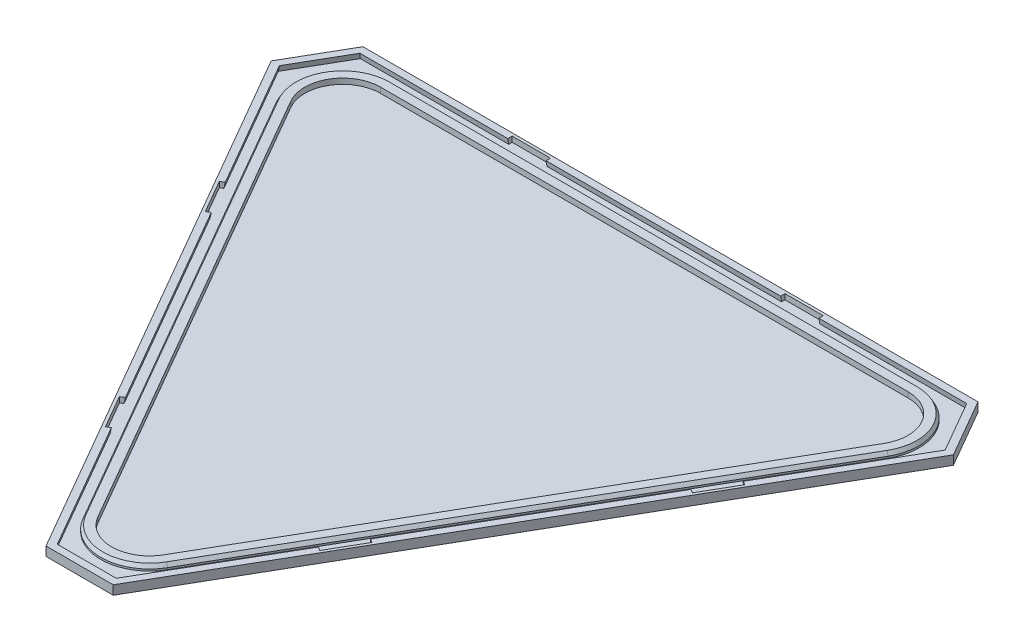
SolidWorks part; units mm, degrees
ref_plane "Plan de face" through (0, 0, 0) normal (0, 0, 1) x (1, 0, 0)
ref_plane "Plan de dessus" through (0, 0, 0) normal (0, 1, 0) x (1, 0, 0)
ref_plane "Plan de droite" through (0, 0, 0) normal (1, 0, 0) x (0, 0, -1)
sketch "Esquisse2" plane through (0, 0, 0) normal (0, 1, 0) x (1, 0, 0)
  line L3 (-93.7624, 43.4671) -> (-52.85, -27.3953) construction
  line L4 (9.2376, -102.9342) -> (50.15, -32.0718) construction
  line L5 (84.5248, 59.4671) -> (2.7, 59.4671) construction
  line L6 (-93.7624, 43.4671) -> (-84.5248, 59.4671)
  line L7 (84.5248, 59.4671) -> (93.7624, 43.4671)
  line L8 (9.2376, -102.9342) -> (-9.2376, -102.9342)
  line L9 (-93.7624, 43.4671) -> (-9.2376, -102.9342)
  line L10 (9.2376, -102.9342) -> (93.7624, 43.4671)
  line L11 (84.5248, 59.4671) -> (-84.5248, 59.4671)
  line L12 (93.7624, 43.4671) -> (84.5248, 59.4671) construction
  line L13 (-9.2376, -102.9342) -> (9.2376, -102.9342) construction
  line L14 (-84.5248, 59.4671) -> (-93.7624, 43.4671) construction
  point P16 (0, 0)
extrude "smartleaf_triangle_multi" add sketch "Esquisse2" along normal blind 1
sketch "Esquisse5" plane through (0, 1, 0) normal (0, 1, 0) x (1, 0, 0)
  line L19 (-93.7624, 43.4671) -> (-9.2376, -102.9342)
  line L20 (-9.2376, -102.9342) -> (9.2376, -102.9342)
  line L21 (9.2376, -102.9342) -> (93.7624, 43.4671)
  line L26 (93.7624, 43.4671) -> (84.5248, 59.4671)
  line L27 (84.5248, 59.4671) -> (-84.5248, 59.4671)
  line L32 (-84.5248, 59.4671) -> (-93.7624, 43.4671)
  line L37 (-93.7624, 43.4671) -> (-9.2376, -102.9342)
  line L38 (-9.2376, -102.9342) -> (9.2376, -102.9342)
  line L39 (9.2376, -102.9342) -> (93.7624, 43.4671)
  line L44 (93.7624, 43.4671) -> (84.5248, 59.4671)
  line L45 (84.5248, 59.4671) -> (-84.5248, 59.4671)
  line L50 (-84.5248, 59.4671) -> (-93.7624, 43.4671)
  dimension "D1" = 0
extrude "Extru.-Mince1" add sketch "Esquisse5" along normal blind 1.5 draft 10 thin draft outward yes thin type one direction reverse wall 1.7
sketch "Esquisse6" plane through (0, 0, 0) normal (0, -1, 0) x (1, 0, 0)
  line L6 (-84.5248, -59.4671) -> (84.5248, -59.4671)
  line L7 (84.5248, -59.4671) -> (93.7624, -43.4671)
  line L8 (93.7624, -43.4671) -> (9.2376, 102.9342)
  line L9 (9.2376, 102.9342) -> (-9.2376, 102.9342)
  line L10 (-9.2376, 102.9342) -> (-93.7624, -43.4671)
  line L11 (-93.7624, -43.4671) -> (-84.5248, -59.4671)
  line L12 (-84.5248, -59.4671) -> (84.5248, -59.4671)
  line L13 (84.5248, -59.4671) -> (93.7624, -43.4671)
  line L14 (93.7624, -43.4671) -> (9.2376, 102.9342)
  line L15 (9.2376, 102.9342) -> (-9.2376, 102.9342)
  line L16 (-9.2376, 102.9342) -> (-93.7624, -43.4671)
  line L17 (-93.7624, -43.4671) -> (-84.5248, -59.4671)
  dimension "D1" = 0
extrude "Enlèv. de mat.-Extru.-Mince1" cut sketch "Esquisse6" against normal through all thin thin type one direction wall 1.5
sketch "Esquisse7" plane through (0, 1, 0) normal (0, 1, 0) x (1, 0, 0)
  line L0 (2.25, 59.4671) -> (-2.25, 59.4671)
  line L1 (2.25, 59.4671) -> (2.25, 55.3671)
  line L2 (-2.25, 59.4671) -> (-2.25, 55.3671)
  line L3 (2.25, 55.3671) -> (-2.25, 55.3671)
  line L4 (-84.5248, 59.4671) -> (84.5248, 59.4671) construction
  line L5 (46.8243, -29.6321) -> (49.0743, -25.735)
  line L6 (50.375, -31.6821) -> (46.8243, -29.6321)
  line L7 (50.375, -31.6821) -> (52.625, -27.785)
  line L8 (52.625, -27.785) -> (49.0743, -25.735)
  line L9 (-49.0743, -25.735) -> (-46.8243, -29.6321)
  line L10 (-52.625, -27.785) -> (-49.0743, -25.735)
  line L11 (-52.625, -27.785) -> (-50.375, -31.6821)
  line L12 (-50.375, -31.6821) -> (-46.8243, -29.6321)
  point P6 (0, 59.4671)
  point P7 (0, 59.4671)
  point P19 (0, 0)
  dimension "D1" = 4.1
  dimension "D2" = 4.5
  dimension "D3" = 3
extrude "Boss.-Extru.5" [suppressed] add sketch "Esquisse7" along normal up to surface (1.5 mm away)
sketch "Esquisse8" [suppressed] plane through (0, 1, 0) normal (0, 1, 0) x (1, 0, 0)
  line L0 (-2.25, 40.6446) -> (2.25, 40.6446) construction
  line L1 (-5, 40.6446) -> (5, 40.6446)
  line L2 (-5, 40.6446) -> (-5, 38.6446)
  line L3 (-5, 38.6446) -> (5, 38.6446)
  line L4 (5, 40.6446) -> (5, 38.6446)
  line L5 (37.6993, -15.9922) -> (32.6993, -24.6524)
  line L6 (37.6993, -15.9922) -> (35.9672, -14.9922)
  line L7 (35.9672, -14.9922) -> (30.9672, -23.6524)
  line L8 (32.6993, -24.6524) -> (30.9672, -23.6524)
  line L9 (-32.6993, -24.6524) -> (-37.6993, -15.9922)
  line L10 (-32.6993, -24.6524) -> (-30.9672, -23.6524)
  line L11 (-30.9672, -23.6524) -> (-35.9672, -14.9922)
  line L12 (-37.6993, -15.9922) -> (-35.9672, -14.9922)
  point P7 (0, 40.6446)
  point P8 (0, 40.6446)
  point P18 (0, 0)
  dimension "D1" = 10
  dimension "D2" = 2
  dimension "D3" = 3
extrude "Boss.-Extru.6" [suppressed] add sketch "Esquisse8" along normal blind 2.2
sketch "Esquisse9" [suppressed] plane through (0, 3.2, 0) normal (0, 1, 0) x (1, 0, 0)
  line L1 (0.6, 40.9446) -> (-0.6, 40.9446)
  line L2 (0.6, 40.9446) -> (0.6, 38.6446)
  line L3 (0.6, 38.6446) -> (-0.6, 38.6446)
  line L4 (-0.6, 40.9446) -> (-0.6, 38.6446)
  line L6 (35.1591, -20.9919) -> (35.7591, -19.9527)
  line L7 (35.1591, -20.9919) -> (33.1672, -19.8419)
  line L8 (33.1672, -19.8419) -> (33.7672, -18.8027)
  line L9 (35.7591, -19.9527) -> (33.7672, -18.8027)
  line L10 (-35.7591, -19.9527) -> (-35.1591, -20.9919)
  line L11 (-35.7591, -19.9527) -> (-33.7672, -18.8027)
  line L12 (-33.7672, -18.8027) -> (-33.1672, -19.8419)
  line L13 (-35.1591, -20.9919) -> (-33.1672, -19.8419)
  line L14 (-2.25, 40.6446) -> (2.25, 40.6446) construction
  line L15 (5, 40.6446) -> (-5, 40.6446) construction
  line L16 (-5, 38.6446) -> (5, 38.6446) construction
  point P4 (0, 40.9446)
  point P9 (0, 40.6446)
  point P21 (0, 0)
  dimension "D1" = 1.2
  dimension "D2" = 3
  dimension "D3" = 0.3
extrude "Boss.-Extru.7" [suppressed] add sketch "Esquisse9" along normal blind 3 and the other way up to next
sketch "Esquisse10" plane through (0, 2.5, 0) normal (0, 1, 0) x (1, 0, 0)
  line L0 (0, 59.4671) -> (0, 32.7785) construction
  line L1 (-32.25, 58.7026) -> (-42.75, 58.7026)
  line L2 (-32.25, 58.7026) -> (-32.25, 39.7025)
  line L3 (-32.25, 39.7025) -> (-42.75, 39.7025)
  line L4 (-42.75, 58.7026) -> (-42.75, 39.7025)
  line L5 (83.3906, 57.5026) -> (-83.3906, 57.5026) construction
  line L7 (-84.5248, 59.4671) -> (84.5248, 59.4671) construction
  line L8 (42.75, 58.7026) -> (42.75, 39.7025)
  line L9 (32.25, 39.7025) -> (42.75, 39.7025)
  line L10 (32.25, 58.7026) -> (32.25, 39.7025)
  line L11 (32.25, 58.7026) -> (42.75, 58.7026)
  line L12 (66.9629, -1.422) -> (72.2129, 7.6713)
  line L13 (66.9629, -1.422) -> (50.5084, 8.0781)
  line L14 (50.5084, 8.0781) -> (55.7584, 17.1713)
  line L15 (72.2129, 7.6713) -> (55.7584, 17.1713)
  line L16 (29.4629, -66.3739) -> (13.0084, -56.8738)
  line L17 (18.2584, -47.7806) -> (13.0084, -56.8738)
  line L18 (34.7129, -57.2806) -> (18.2584, -47.7806)
  line L19 (34.7129, -57.2806) -> (29.4629, -66.3739)
  line L20 (-34.7129, -57.2806) -> (-29.4629, -66.3739)
  line L21 (-34.7129, -57.2806) -> (-18.2584, -47.7806)
  line L22 (-18.2584, -47.7806) -> (-13.0084, -56.8738)
  line L23 (-29.4629, -66.3739) -> (-13.0084, -56.8738)
  line L24 (-72.2129, 7.6713) -> (-55.7584, 17.1713)
  line L25 (-50.5084, 8.0781) -> (-55.7584, 17.1713)
  line L26 (-66.9629, -1.422) -> (-50.5084, 8.0781)
  line L27 (-66.9629, -1.422) -> (-72.2129, 7.6713)
  point P11 (-37.5, 58.7026)
  point P35 (0, 0)
  dimension "D1" = 1.2
  dimension "D2" = 10.5
  dimension "D3" = 75
  dimension "D4" = 3
extrude "Enlèv. mat.-Extru.1" cut sketch "Esquisse10" against normal up to surface (1.5 mm away) up to face at (0, 1, 0)
sketch "Esquisse11" plane through (0, 1, 0) normal (0, 1, 0) x (1, 0, 0)
  line L6 (-12.1244, -90.9342) -> (-47.1189, -30.3218) construction
  line L7 (84.8135, 34.9671) -> (49.8189, -25.6453) construction
  line L8 (2.7, 55.9671) -> (72.6891, 55.9671) construction
  line L12 (11.6127, -90.4204) -> (84.1127, 35.1533)
  line L13 (-84.1127, 35.1533) -> (-11.6127, -90.4204)
  line L14 (72.5, 55.2671) -> (-72.5, 55.2671)
  arc A9 (84.1127, 35.1533) -> (72.5, 55.2671) centre (72.5, 41.8579) ccw
  arc A10 (-11.6127, -90.4204) -> (11.6127, -90.4204) centre (0, -83.7158) ccw
  arc A11 (-72.5, 55.2671) -> (-84.1127, 35.1533) centre (-72.5, 41.8579) ccw
  point P0 (0, -82.957)
  dimension "D4" = 145
  dimension "D1" = 0.7
  dimension "D2" = 0.7
  dimension "D3" = 0.7
extrude "Extru.-Mince2" add sketch "Esquisse11" along normal up to surface (1.5 mm away) separate body thin up to face at (0, 2.5, 0) thin type one direction reverse wall 3
sketch "Esquisse12" plane through (0, 1, 0) normal (0, 1, 0) x (1, 0, 0)
  line L0 (72.5, 52.2671) -> (-72.5, 52.2671) construction
  line L1 (-7.5, 40.7446) -> (7.5, 40.7446)
  line L2 (-7.5, 40.7446) -> (-7.5, 52.2671)
  line L3 (-7.5, 52.2671) -> (7.5, 52.2671)
  line L4 (7.5, 40.7446) -> (7.5, 52.2671)
  line L5 (-7.5, 35.7446) -> (-7.5, 40.7446) construction
  line L6 (7.5, 40.7446) -> (7.5, 35.7446) construction
  line L7 (1.75, 40.7446) -> (9.5, 40.7446) construction
  dimension "D1" = 0
  dimension "D2" = 0
  dimension "D3" = 0
extrude "Boss.-Extru.8" [suppressed] add sketch "Esquisse12" along normal blind 2
ref_axis "Axe1" through (0, 0, 0) along (0, 1, 0)
pattern_circular "Répétition circulaire1" [suppressed] count 3 over 360 about axis through (0, 0, 0) along (0, 1, 0) of bodies 113
chamfer "Chanfrein2" [suppressed] distance 0.5 angle 45
chamfer "Chanfrein1" distance 1 angle 30 6 edges at (-84.1127, 2.5, -48.5625) (84.1127, 2.5, -48.5625) (0, 2.5, 97.125) (47.8627, 2.5, 27.6335) (-47.8627, 2.5, 27.6335) (0, 2.5, -55.2671) first distance on face at (-81.2095, 1.75, -46.8863) first distance on face at (81.2095, 1.75, -46.8863) first distance on face at (0, 1.75, 93.7727) first distance on face at (47.8627, 1.75, 27.6335) first distance on face at (-47.8627, 1.75, 27.6335) first distance on face at (0, 1.75, -55.2671)
